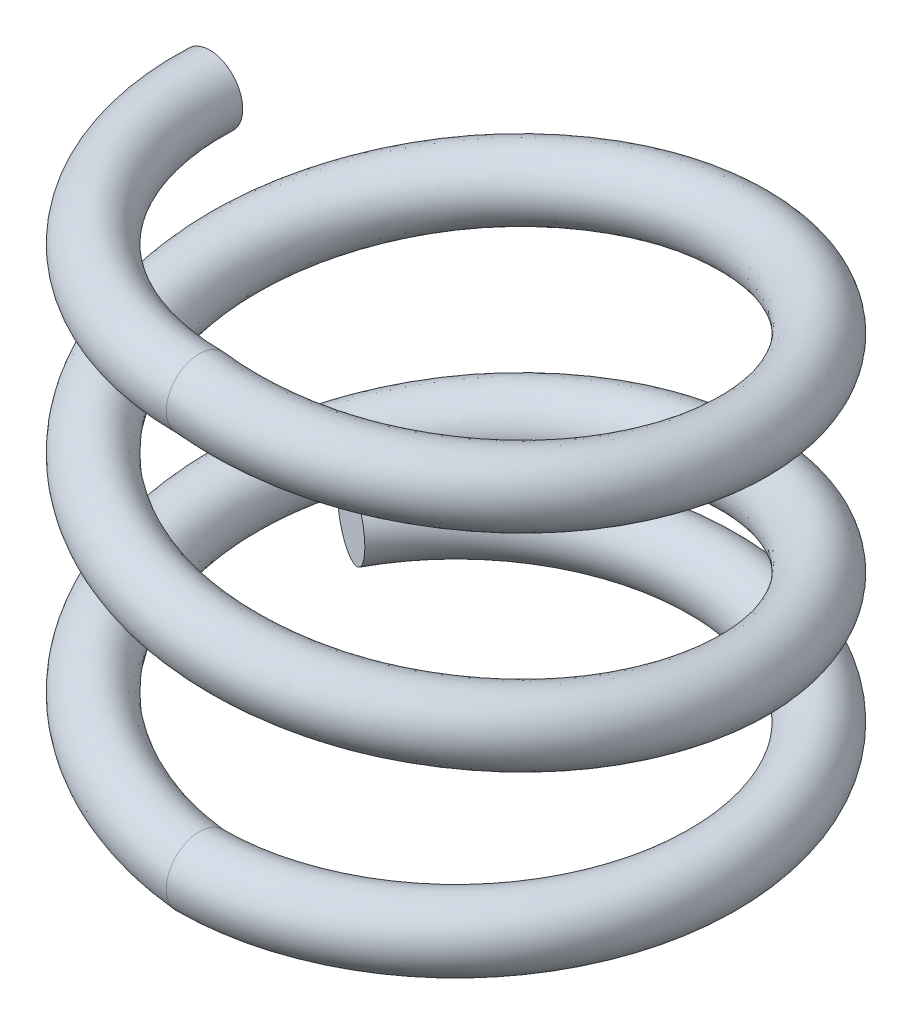
SolidWorks part; units mm, degrees
ref_plane "Front Plane" through (0, 0, 0) normal (0, 0, 1) x (1, 0, 0)
ref_plane "Top Plane" through (0, 0, 0) normal (0, 1, 0) x (1, 0, 0)
ref_plane "Right Plane" through (0, 0, 0) normal (1, 0, 0) x (0, 0, -1)
sketch "Sketch1" plane through (0, 0, 0) normal (0, 1, 0) x (1, 0, 0)
  circle A0 centre (0, 0) radius 3.1
  dimension "D1" = 6.2
curve "Helix/Spiral1" pitch 2.5 height 5 radius 3.1 left hand yes centre (0, 0, 0) axis (0, 1, 0) start towards (0, 0, 1)
sketch "Sketch3" plane through (0, 0, 0) normal (1, 0, 0) x (0, 0, -1)
  circle A0 centre (-3.1, 0) radius 0.4
  spline S0 degree 3 poles (-3.1, 0) (-3.1, 0.0518) (-2.9386, 0.1564) (-2.2491, 0.3125) (-1.2172, 0.4688) (0, 0.625) (1.2172, 0.7813) (2.2491, 0.9375) (2.9386, 1.0938) (3.1807, 1.25) (2.9386, 1.4063) (2.2491, 1.5625) (0.8732, 1.7708) (-0.8732, 1.9792) (-2.2491, 2.1875) (-2.9386, 2.3438) (-3.1807, 2.5) (-2.9386, 2.6562) (-2.2491, 2.8125) (-0.8732, 3.0208) (0.8732, 3.2292) (2.2491, 3.4375) (2.9386, 3.5937) (3.1807, 3.75) (2.9386, 3.9062) (2.2491, 4.0625) (1.2172, 4.2187) (0, 4.375) (-1.2172, 4.5312) (-2.2491, 4.6875) (-2.9386, 4.8436) (-3.1, 4.9482) (-3.1, 5) knots 0 0 0 0 0.03125 0.0625 0.09375 0.125 0.15625 0.1875 0.21875 0.25 0.28125 0.3125 0.34375 0.40625 0.4375 0.46875 0.5 0.53125 0.5625 0.59375 0.65625 0.6875 0.71875 0.75 0.78125 0.8125 0.84375 0.875 0.90625 0.9375 0.96875 1 1 1 1 construction
  dimension "D1" = 0.8
sweep "Sweep2" add profiles "Sketch3" path "Helix/Spiral1"
sketch "Sketch7" plane through (0, 0, 0) normal (0, 1, 0) x (1, 0, 0)
  line L0 (0, -3.5) -> (0, -2.7) construction
  arc A0 (0, -3.1) -> (-2.7314, 1.4662) centre (0, 0) ccw
  dimension "D1" = 6.2
sketch "Sketch8" plane through (0, 0, 0) normal (1, 0, 0) x (0, 0, -1)
  line L0 (3.1, 0) -> (-3.1, 0) construction
  circle A0 centre (-3.1, 0) radius 0.4
sweep "Sweep3" add profiles "Sketch8" path "Sketch7"
sketch "Sketch10" plane through (0, 0, 0) normal (-1, 0, 0) x (0, 0, 1)
  circle A0 centre (3.1, 5) radius 0.4
  circle A1 centre (3.1, 5) radius 0.4 construction
  point P2 (3.1, 5)
ref_plane "Plane1" through (0, 5, 0) normal (0, 1, 0) x (1, 0, 0)
sketch "Sketch12" plane through (0, 5, 0) normal (0, 1, 0) x (1, 0, 0)
  arc A0 (0, -3.1) -> (-3.0969, 0.1388) centre (0, 0) cw
sweep "Sweep4" add profiles "Sketch10" path "Sketch12"
sketch "Sketch4" plane through (0, 0, 0) normal (1, 0, 0) x (0, 0, -1)
  line L0 (0.3739, 5.4) -> (0.1388, 5.4) construction
  line L1 (-3.1, -0.4) -> (-4.5425, -0.4) construction
  circle A3 centre (-3.1, 0) radius 0.4 construction
  ellipse E0 centre (0.1388, 5) end of major axis (0.1388, 4.6) minor radius 0.0179 construction
sketch "Sketch5" plane through (0, 0, 0) normal (0, 1, 0) x (1, 0, 0)
  circle A0 centre (0, 0) radius 3.5 construction
  circle A1 centre (0, 0) radius 2.7 construction
  circle A2 centre (0, 0) radius 3.1 construction
  dimension "D1" = 7
  dimension "D2" = 6.2
  dimension "D3" = 5.4
ref_axis "Axis1" through (0, 5.69, 0) along (0, -1, 0)
ref_plane "Bottom of Spring" through (0, -0.4, 0) normal (0, 1, 0) x (1, 0, 0)
ref_plane "Top of Spring" through (0, 5.4, 0) normal (0, 1, 0) x (1, 0, 0)
